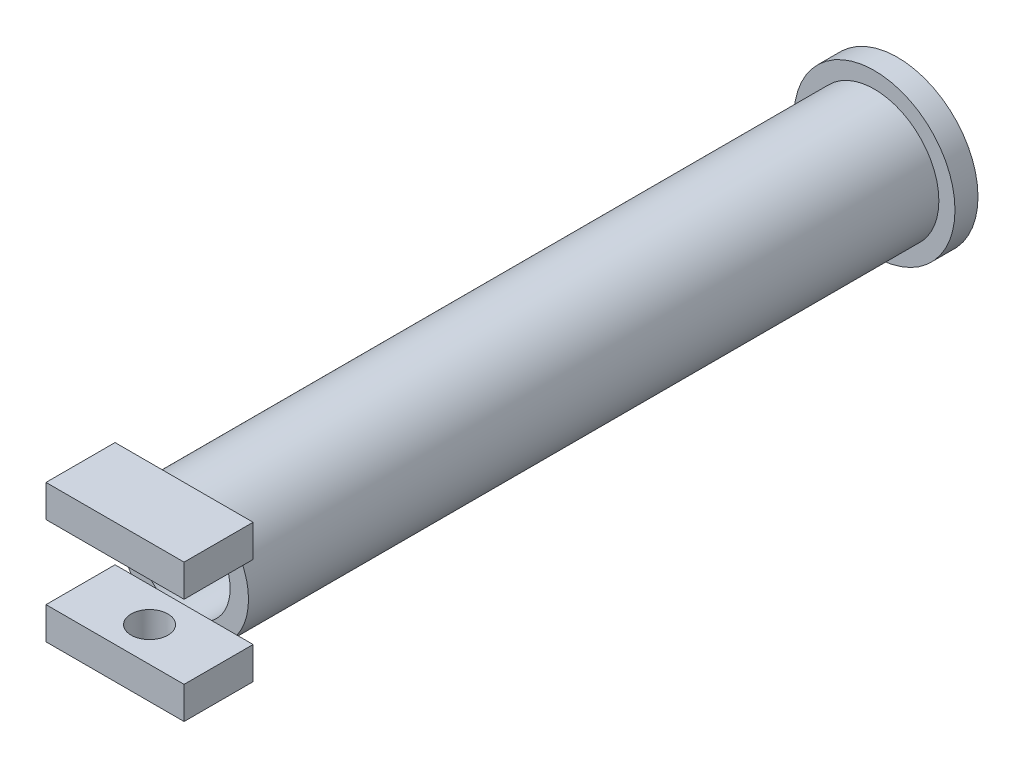
SolidWorks part; units mm, degrees
ref_plane "前视基准面" through (0, 0, 0) normal (0, 0, 1) x (1, 0, 0)
ref_plane "上视基准面" through (0, 0, 0) normal (0, 1, 0) x (1, 0, 0)
ref_plane "右视基准面" through (0, 0, 0) normal (1, 0, 0) x (0, 0, -1)
other "Configuration Table"
sketch "Sketch1" plane through (0, 0, 0) normal (0, 0, 1) x (1, 0, 0)
  circle A0 centre (0, 0) radius 17.5
extrude "Boss-Extrude1" add sketch "Sketch1" along normal blind 5
sketch "Sketch2" plane through (0, 0, 0) normal (0, 0, 1) x (1, 0, 0)
  circle A0 centre (0, 0) radius 14
extrude "Boss-Extrude2" add sketch "Sketch2" along normal blind 155
ref_plane "Plane1" through (0, 0, 155) normal (0, 0, 1) x (1, 0, 0)
sketch "Sketch3" plane through (0, 0, 155) normal (0, 0, 1) x (1, 0, 0)
  circle A0 centre (0, 0) radius 10
extrude "Cut-Extrude2" cut sketch "Sketch3" against normal blind 150
sketch "Sketch4" plane through (0, 0, 155) normal (0, 0, 1) x (1, 0, 0)
  line L1 (-15, -15) -> (15, -15)
  line L2 (-15, -15) -> (-15, 15)
  line L3 (-15, 15) -> (15, 15)
  line L4 (15, -15) -> (15, 15)
  line L5 (-15, -15) -> (15, 15) construction
  line L6 (-15, 15) -> (15, -15) construction
  point P0 (0, 0)
extrude "Boss-Extrude3" add sketch "Sketch4" along normal blind 15
ref_plane "Plane2" through (0, 0, 170) normal (0, 0, 1) x (1, 0, 0)
sketch "Sketch5" plane through (0, 0, 170) normal (0, 0, 1) x (1, 0, 0)
  line L0 (15, -15) -> (15, 15) construction
  line L1 (-15, -8) -> (15, -8)
  line L2 (-15, -8) -> (-15, 8)
  line L3 (-15, 8) -> (15, 8)
  line L4 (15, -8) -> (15, 8)
  line L5 (-15, -8) -> (15, 8) construction
  line L6 (-15, 8) -> (15, -8) construction
  point P0 (0, 0)
extrude "Cut-Extrude3" cut sketch "Sketch5" against normal blind 15
ref_plane "Plane3" through (0, 11.5, 0) normal (0, 1, 0) x (1, 0, 0)
sketch "Sketch6" plane through (0, 11.5, 0) normal (0, 1, 0) x (1, 0, 0)
  circle A0 centre (0, -162.5) radius 4
extrude "Cut-Extrude4" cut sketch "Sketch6" against normal blind 30
ref_plane "bottom_flange_face" through (0, 0, 0) normal (0, 0, 1) x (1, 0, 0)
ref_plane "top_joint_side_left" through (0, 8, 0) normal (0, 1, 0) x (1, 0, 0)
ref_plane "top_joint_side_right" through (0, -8, 0) normal (0, 1, 0) x (1, 0, 0)
sketch3d "3DSketch1"
  line L0 (0, 0, 0) -> (0, 0, 1000) construction
ref_axis "column_main_axis" through (0, 0, 0) along (0, 0, 1)
sketch3d "3DSketch2"
  line L0 (0, -1000, 162.5) -> (0, 1000, 162.5) construction
ref_axis "pitch1_axis" through (0, -1000, 162.5) along (0, 1, 0)
